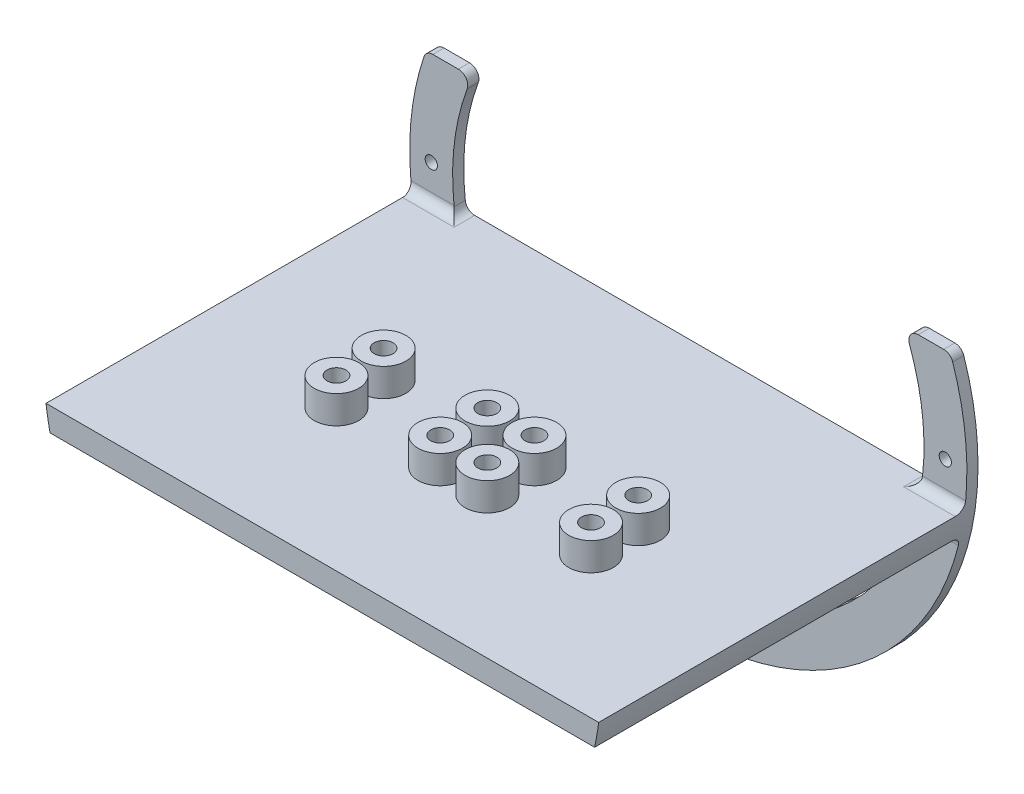
SolidWorks part; units mm, degrees
ref_plane "Front Plane" through (0, 0, 0) normal (0, 0, 1) x (1, 0, 0)
ref_plane "Top Plane" through (0, 0, 0) normal (0, 1, 0) x (1, 0, 0)
ref_plane "Right Plane" through (0, 0, 0) normal (1, 0, 0) x (0, 0, -1)
sketch "Sketch1" plane through (0, 0, 0) normal (0, 0, 1) x (1, 0, 0)
  line L0 (-70.6286, 25.4) -> (-58.1987, 25.4)
  line L1 (58.1987, 25.4) -> (70.6286, 25.4)
  line L3 (-74.4502, -9.525) -> (74.4502, -9.525)
  line L5 (-73.359, -15.875) -> (73.359, -15.875)
  arc A0 (-70.6286, 25.4) -> (70.6286, 25.4) centre (0, 0) ccw
  arc A1 (-58.1987, 25.4) -> (58.1987, 25.4) centre (0, 0) ccw
  dimension "D1" = 75.057
  dimension "D2" = 63.5
  dimension "D3" = 25.4
  dimension "D4" = 6.35
  dimension "D5" = 9.525
extrude "Boss-Extrude1" add sketch "Sketch1" along normal blind 3 contours A1 L0 A0 L3 | A1 L5 A0 | A1 L3 A0 L1 region at (-68.0281, 8.118, 0) region at (-67.4213, -17.457, 0) region at (68.0281, 8.118, 0)
extrude "Boss-Extrude2" add sketch "Sketch1<3>" along normal blind 101.6 contours A1 L3 A0 L5 | L3 A1 L5 | A1 L5 A0 L3 region at (-68.0684, -12.7093, 0) region at (0, -12.689, 0) region at (68.0684, -12.7093, 0)
sketch "Sketch1<3>" plane through (0, 0, 0) normal (0, 0, 1) x (1, 0, 0) same geometry as "Sketch1"
sketch "Sketch2" plane through (0, -9.525, 0) normal (0, 1, 0) x (1, 0, 0)
  line L0 (0, 7.7486) -> (0, -118.2987) construction
  line L1 (-62.7816, 0) -> (62.7816, 0) construction
  circle A0 centre (-34.29, -50.8) radius 6
  circle A1 centre (-6.35, -50.8) radius 6
  circle A2 centre (-34.29, -63.5) radius 6
  circle A3 centre (-6.35, -63.5) radius 6
  circle A4 centre (6.35, -63.5) radius 6
  circle A5 centre (34.29, -63.5) radius 6
  circle A6 centre (6.35, -50.8) radius 6
  circle A7 centre (34.29, -50.8) radius 6
  circle A8 centre (-34.29, -63.5) radius 2.5527
  circle A9 centre (-34.29, -50.8) radius 2.5527
  circle A10 centre (-6.35, -50.8) radius 2.5527
  circle A11 centre (-6.35, -63.5) radius 2.5527
  circle A12 centre (-6.35, -50.8) radius 6
  circle A13 centre (6.35, -50.8) radius 6
  circle A14 centre (6.35, -63.5) radius 2.5527
  circle A15 centre (34.29, -63.5) radius 2.5527
  circle A16 centre (6.35, -50.8) radius 2.5527
  circle A17 centre (34.29, -50.8) radius 2.5527
  dimension "D5" = 12
  dimension "D6" = 5.1054
  dimension "D1" = 12.7
  dimension "D2" = 27.94
  dimension "D3" = 6.35
  dimension "D4" = 50.8
extrude "Boss-Extrude3" add sketch "Sketch2" along normal blind 7.54 contours A2 A8 | A0 A9 | A1 A10 | A3 A11 | A4 A14 | A6 A16 | A7 A17 | A5 A15 region at (-40.1203, -9.525, 50.8) region at (-12.1803, -9.525, 50.8) region at (-40.1203, -9.525, 63.5) region at (-12.1803, -9.525, 63.5) region at (0.5197, -9.525, 63.5) region at (28.4597, -9.525, 63.5) region at (0.5197, -9.525, 50.8) region at (28.4597, -9.525, 50.8)
extrude "Cut-Extrude1" cut sketch "Sketch2<3>" against normal through all contours A9 | A10 | A16 | A17 | A15 | A14 | A11 | A8 region at (-34.29, -9.525, 63.5) region at (-34.29, -9.525, 50.8) region at (-6.35, -9.525, 50.8) region at (-6.35, -9.525, 63.5) region at (6.35, -9.525, 63.5) region at (34.29, -9.525, 63.5) region at (6.35, -9.525, 50.8) region at (34.29, -9.525, 50.8)
sketch "Sketch2<3>" plane through (0, -9.525, 0) normal (0, 1, 0) x (1, 0, 0) same geometry as "Sketch2"
sketch "Sketch3" plane through (0, 0, 3) normal (0, 0, 1) x (1, 0, 0)
  line L0 (-70.6286, 25.4) -> (-58.1987, 25.4) construction
  circle A0 centre (0, -69.2407) radius 1.65
  circle A1 centre (69.2407, 0) radius 1.65
  circle A2 centre (-69.2407, 0) radius 1.65
  circle A3 centre (0, 0) radius 69.2407 construction
  point P11 (-64.4136, 25.4)
  dimension "D1" = 3.3
extrude "Cut-Extrude2" cut sketch "Sketch3" against normal through all
fillet "Fillet1" radius 2.54 4 edges at (70.6286, 25.4, 1.5) (58.1987, 25.4, 1.5) (-70.6286, 25.4, 1.5) (-58.1987, 25.4, 1.5)
fillet "Fillet2" radius 2.54 4 edges at (-67.4213, -15.875, 3) (-68.6159, -9.525, 3) (68.6159, -9.525, 3) (67.4213, -15.875, 3)
fillet "Fillet3" radius 2.54 4 edges at (62.7816, -9.525, 2.77) (61.4836, -15.875, 2.77) (-61.4836, -15.875, 2.77) (-62.7816, -9.525, 2.77)
